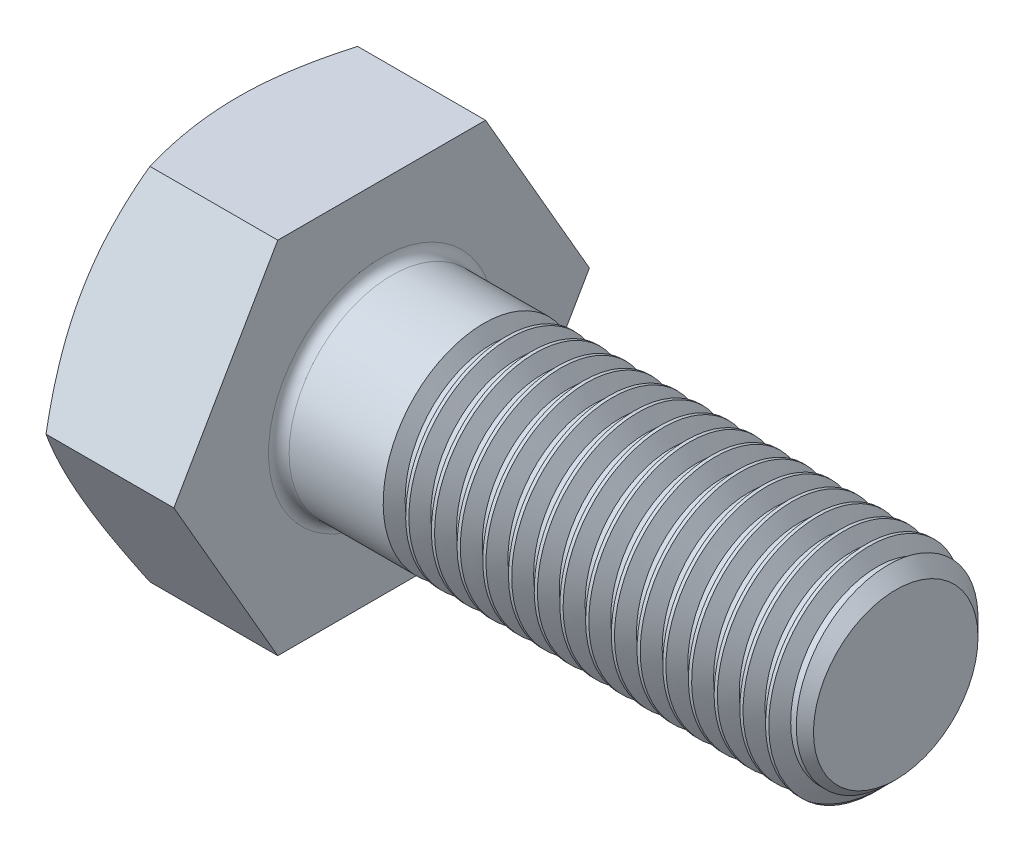
SolidWorks part; units mm, degrees
ref_plane "前视基准面" through (0, 0, 0) normal (0, 0, 1) x (1, 0, 0)
ref_plane "上视基准面" through (0, 0, 0) normal (0, 1, 0) x (1, 0, 0)
ref_plane "右视基准面" through (0, 0, 0) normal (1, 0, 0) x (0, 0, -1)
sketch "草图1" plane through (0, 0, 0) normal (1, 0, 0) x (0, 0, -1)
  line L1 (4.0415, 0) -> (2.0207, 3.5)
  line L2 (2.0207, 3.5) -> (-2.0207, 3.5)
  line L3 (-2.0207, 3.5) -> (-4.0415, 0)
  line L4 (-4.0415, 0) -> (-2.0207, -3.5)
  line L5 (-2.0207, -3.5) -> (2.0207, -3.5)
  line L6 (2.0207, -3.5) -> (4.0415, 0)
  circle A0 centre (0, 0) radius 3.5 construction
  dimension "D1" = 7
extrude "拉伸1" add sketch "草图1" along normal blind 2.8
sketch "草图2" plane through (0, 0, 0) normal (-1, 0, 0) x (0, 0, 1)
  circle A0 centre (0, 0) radius 3.5
  dimension "D1" = 7
sketch "草图3" plane through (0, 0, 0) normal (0, 1, 0) x (1, 0, 0)
  line L0 (-18.0603, 0) -> (41.5769, 0) construction
  line L1 (0, 3.5) -> (0.3126, 4.0415)
  line L2 (0, 3.5) -> (0, -3.5)
  line L3 (0, 3.5) -> (0, -3.5)
  line L4 (2.8, 4.0415) -> (0, 4.0415) construction
  line L5 (0, 3.5) -> (0, 4.0415)
  line L6 (0, 4.0415) -> (0.3126, 4.0415)
  dimension "D2" = 30
  dimension "D1" = 0
revolve "切除-旋转2" cut sketch "草图3" angle 360 about L0
sketch "草图4" plane through (2.8, 0, 0) normal (1, 0, 0) x (0, 0, -1)
  circle A0 centre (0, 0) radius 2
  dimension "D1" = 4
extrude "拉伸2" add sketch "草图4" along normal blind 10
chamfer "倒角1" distance 0.4 angle 45 1 edges at (12.8, 0, -2)
sketch "草图5" plane through (0, 0, 0) normal (0, 1, 0) x (1, 0, 0)
  line L0 (217.2267, 2) -> (226.9644, 2) construction
  line L1 (12.4, 2) -> (2.8, 2) construction
  line L2 (12.8, 12.6777) -> (12.8, 22.4507) construction
  line L3 (12.8, -1.6) -> (12.8, 1.6) construction
  line L4 (12.7375, 1.7294) -> (12.5812, 2)
  line L5 (12.8625, 1.7294) -> (13.0187, 2)
  line L6 (12.5812, 2) -> (13.0187, 2)
  line L7 (12.7375, 1.7294) -> (12.8625, 1.7294)
  dimension "D1" = 30
  dimension "D2" = 30
  dimension "D3" = 0.4375
  dimension "D4" = 0.125
sketch "草图6" plane through (12.8, 0, 0) normal (1, 0, 0) x (0, 0, -1)
  circle A0 centre (0, 0) radius 2
  dimension "D1" = 4
curve "螺旋线1" pitch 0.5 height 8 radius 2 centre (12.8, 0, 0) axis (-1, 0, 0) start towards (0, 0, -1)
sweep "切除-扫描1" cut profiles "草图5" path "螺旋线1"
fillet "圆角1" radius 0.2 1 edges at (2.8, 0, -2) type face fillet first side face at (2.8, 0, -2) second side face at (2.8, 0, 0)
